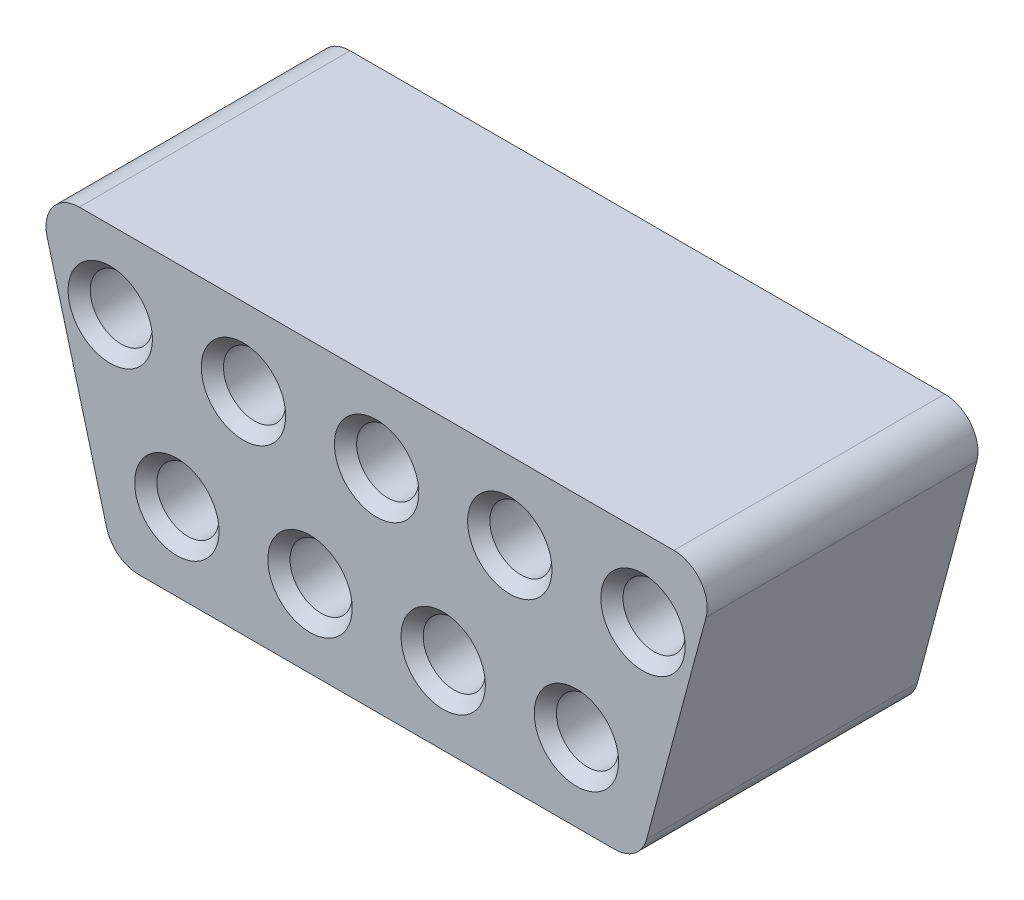
SolidWorks part; units mm, degrees
ref_plane "Front Plane" through (0, 0, 0) normal (0, 0, 1) x (1, 0, 0)
ref_plane "Top Plane" through (0, 0, 0) normal (0, 1, 0) x (1, 0, 0)
ref_plane "Right Plane" through (0, 0, 0) normal (1, 0, 0) x (0, 0, -1)
sketch "Sketch1" plane through (0, 0, 0) normal (0, 0, 1) x (1, 0, 0)
  line L0 (-135.2667, 0) -> (178.1738, 0) construction
  line L1 (0, 93.814) -> (0, -102.1772) construction
  line L3 (-5.3573, -3.25) -> (5.3573, -3.25)
  line L4 (7.4215, 2.3059) -> (6.0818, -2.6941)
  line L5 (-6.6971, 3.25) -> (6.6971, 3.25)
  line L6 (-7.4215, 2.3059) -> (-6.0818, -2.6941)
  line L7 (-15.45, 6.25) -> (15.45, -6.25) construction
  line L8 (-15.45, -6.25) -> (15.45, 6.25) construction
  line L13 (-8.25, 4) -> (8.25, -4) construction
  line L14 (-8.25, -4) -> (8.25, 4) construction
  arc A0 (5.3573, -3.25) -> (6.0818, -2.6941) centre (5.3573, -2.5) ccw
  arc A1 (7.4215, 2.3059) -> (6.6971, 3.25) centre (6.6971, 2.5) ccw
  arc A6 (-7.4215, 2.3059) -> (-6.6971, 3.25) centre (-6.6971, 2.5) cw
  arc A7 (-6.0818, -2.6941) -> (-5.3573, -3.25) centre (-5.3573, -2.5) ccw
  point P5 (0, 0)
  point P14 (0, 0)
  dimension "D1" = 16.5
  dimension "D3" = 30.9
  dimension "D5" = 12.5
extrude "Boss-Extrude1" add sketch "Sketch1" along normal blind 6.1 contours L6 A7 L3 A0 L4 A1 L5 A6 region at (0, 0.1291, 0)
sketch "Sketch2" plane through (0, 0, 6.1) normal (0, 0, 1) x (1, 0, 0)
  line L0 (-8.2519, 0) -> (8.6621, 0) construction
  line L1 (-8.8741, 1.5) -> (8.245, 1.5) construction
  line L2 (-7.4215, 2.3059) -> (-6.0818, -2.6941) construction
  circle A0 centre (-5.9995, 1.5) radius 0.7
  circle A1 centre (-2.9995, 1.5) radius 0.7
  circle A2 centre (0.0005, 1.5) radius 0.7
  circle A3 centre (3.0005, 1.5) radius 0.7
  circle A4 centre (6.0005, 1.5) radius 0.7
  circle A5 centre (-4.4995, -1.5) radius 0.7
  circle A6 centre (-1.4995, -1.5) radius 0.7
  circle A7 centre (1.5005, -1.5) radius 0.7
  circle A8 centre (4.5005, -1.5) radius 0.7
  dimension "D1" = 1.165
  dimension "D3" = 1.5
  dimension "D5" = 1.4
  dimension "D7" = 1.4
  dimension "D2" = 1.5
  dimension "D4" = 1.5
  dimension "D6" = 5
  dimension "D8" = 4
extrude "Cut-Extrude1" cut sketch "Sketch2" against normal up to next
chamfer "Chamfer1" distance 0.25 angle 45 9 edges at (-3.7995, -1.5, 6.1) (-0.7995, -1.5, 6.1) (2.2005, -1.5, 6.1) (5.2005, -1.5, 6.1) (6.7005, 1.5, 6.1) (3.7005, 1.5, 6.1) (0.7005, 1.5, 6.1) (-2.2995, 1.5, 6.1) (-5.2995, 1.5, 6.1)
